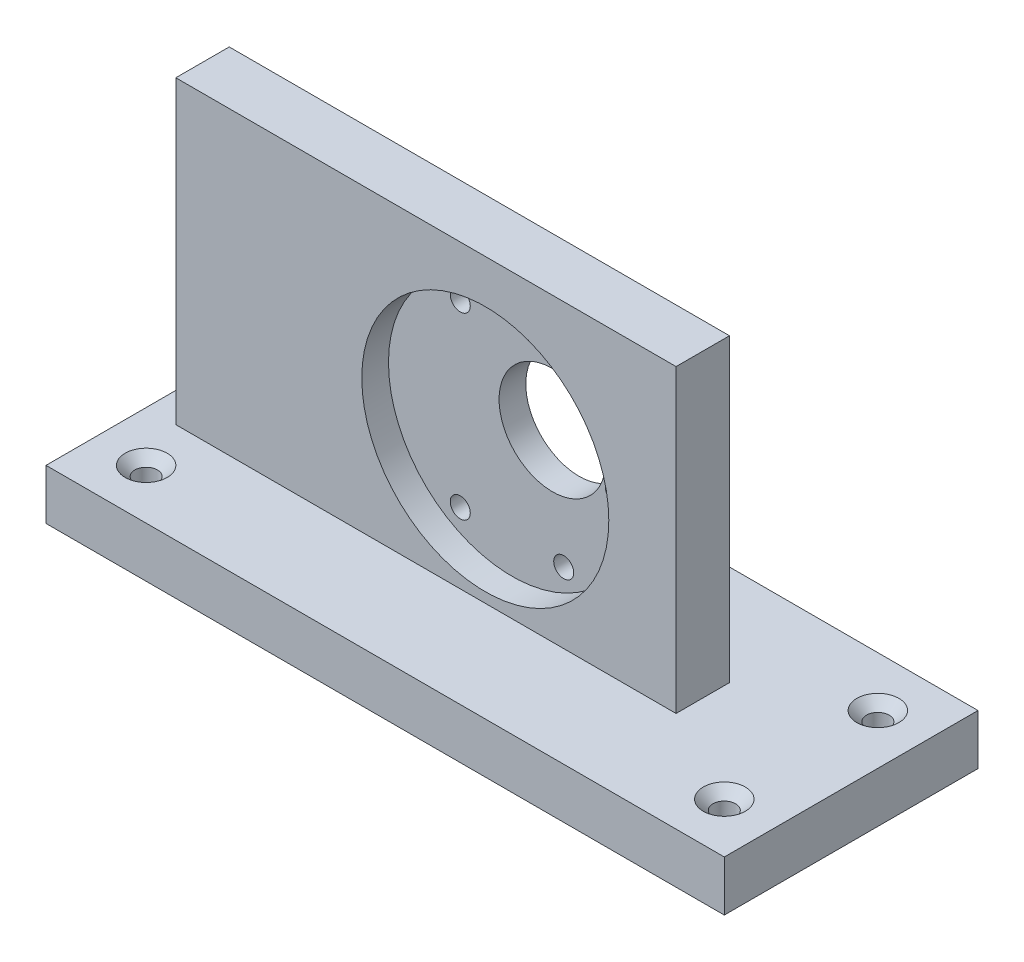
SolidWorks part; units mm, degrees
note: The reader was unsure of these and kept them because the rebuilt part matched: shared geometry of "Sketch3<3>".
other "Markup1"
sketch "Sketch5" plane through (25, 50, 8) normal (0.9645, 0.1424, 0.2224) x (0.1697, 0.3107, -0.9352)
ref_plane "Front Plane" through (0, 0, 0) normal (0, 0, 1) x (1, 0, 0)
ref_plane "Top Plane" through (0, 0, 0) normal (0, 1, 0) x (1, 0, 0)
ref_plane "Right Plane" through (0, 0, 0) normal (1, 0, 0) x (0, 0, -1)
sketch "Sketch3" plane through (0, 0, 0) normal (0, 0, 1) x (1, 0, 0)
  line L1 (-28.575, 50) -> (28.575, 50)
  line L2 (-28.575, 50) -> (-28.575, 0)
  line L3 (-28.575, 0) -> (28.575, 0)
  line L4 (28.575, 50) -> (28.575, 0)
  line L5 (-7.75, 38.4234) -> (7.75, 38.4234) construction
  line L6 (7.75, 38.4234) -> (15.5, 25) construction
  line L7 (15.5, 25) -> (7.75, 11.5766) construction
  line L8 (7.75, 11.5766) -> (-7.75, 11.5766) construction
  line L9 (-7.75, 11.5766) -> (-15.5, 25) construction
  line L10 (-15.5, 25) -> (-7.75, 38.4234) construction
  line L12 (-20.1843, 13.3466) -> (22.8058, 38.167) construction
  circle A5 centre (-7.75, 38.4234) radius 1.5
  circle A6 centre (7.75, 38.4234) radius 1.5
  circle A8 centre (-7.75, 11.5766) radius 1.5
  circle A9 centre (7.75, 11.5766) radius 1.5
  circle A10 centre (15.5, 25) radius 1.5
  circle A11 centre (6.0622, 28.5) radius 8
  point P4 (0, 0)
  point P27 (-11.625, 18.2883)
  point P28 (11.625, 31.7117)
  dimension "D4" = 25
  dimension "D9" = 16
  dimension "D3" = 3
  dimension "D1" = 50
  dimension "D2" = 57.15
  dimension "D6" = 120
  dimension "D7" = 120
  dimension "D8" = 15.5
  dimension "D10" = 6.4234
extrude "Boss-Extrude1" add sketch "Sketch3" along normal blind 8 contours L2 L3 L4 L1
extrude "Cut-Extrude2" cut sketch "Sketch3<3>" along normal blind 10
sketch "Sketch3<3>" plane through (0, 0, 0) normal (0, 0, 1) x (1, 0, 0) same geometry as "Sketch3"
sketch "Sketch4" plane through (0, 0, 8) normal (0, 0, 1) x (1, 0, 0)
  line L0 (-15.5, 25) -> (15.5, 25) construction
  circle A0 centre (0, 25) radius 18.5
  dimension "D1" = 37
extrude "Cut-Extrude3" cut sketch "Sketch4" against normal blind 4 contours A0
sketch "Sketch6" plane through (0, 0, 8) normal (0, 0, 1) x (1, 0, 0)
  line L1 (-50.8, 5) -> (50.8, 5)
  line L2 (-50.8, 5) -> (-50.8, 0)
  line L3 (-50.8, 0) -> (50.8, 0)
  line L4 (50.8, 5) -> (50.8, 0)
  point P4 (0, 0)
  dimension "D1" = 101.6
  dimension "D2" = 5
extrude "Boss-Extrude2" add sketch "Sketch6" against normal blind 23 and the other way blind 15
sketch "Sketch7" plane through (0, 5, 0) normal (0, 1, 0) x (1, 0, 0)
  line L0 (-50.8, -23) -> (-50.8, 15) construction
  line L1 (-50.8, -23) -> (-43.3, -23)
  line L2 (-50.8, -23) -> (-50.8, -15.5)
  line L3 (-50.8, -15.5) -> (-43.3, -15.5)
  line L4 (-43.3, -23) -> (-43.3, -15.5)
  line L5 (-50.8, -4) -> (50.8, -4) construction
  line L6 (50.8, -23) -> (50.8, 15) construction
  line L7 (0, 15) -> (0, -23) construction
  line L8 (50.8, 15) -> (-50.8, 15) construction
  line L9 (50.8, -23) -> (-50.8, -23) construction
  point P18 (-43.3, 7.5)
  point P20 (43.3, -15.5)
  point P21 (43.3, 7.5)
  dimension "D1" = 7.5
hole_wizard "CSK for M3 Flat Head Machine Screw1" positions "Sketch8" profile "Sketch9" countersink size "M3" standard "ANSI Metric" end condition through all
sketch "Sketch8" plane through (0, 5, 0) normal (0, 1, 0) x (1, 0, 0)
  point P0 (-43.3, 7.5)
  point P3 (-43.3, -15.5)
  point P6 (43.3, -15.5)
  point P9 (43.3, 7.5)
sketch "Sketch9" plane through (-43.3, 5, -7.5) normal (1, 0, 0) x (0, 0, 1)
  line L0 (0, 0) -> (0, 5)
  line L1 (0, 5) -> (1.7, 5)
  line L2 (1.7, 5) -> (1.7, 1.45)
  line L3 (1.7, 1.45) -> (3.15, 0)
  line L5 (3.15, 0) -> (0, 0)
  line L6 (-1.7, 1.45) -> (-3.15, 0) construction
  line L11 (0, -6.35) -> (0, 107.95) construction
  dimension "Thru Hole Dia." = 3.4
  dimension "Thru Hole Depth" = 5
  dimension "Near C'Sink Dia." = 6.3
  dimension "Near C'Sink Angle" = 90
extrude "Cut-Extrude6" cut sketch "Sketch16" against normal up to surface (4.826 mm away)
sketch "Sketch16" plane through (-499.2489, 16.8212, -28.3089) normal (0.0361, 0.9993, -0.0009) x (0.0508, -0.0009, 0.9987)
  circle A0 centre (67.5, 464.5) radius 1.7
  circle A2 centre (92.5, 462.5) radius 1.8
  circle A3 centre (113.4, 462.5) radius 1.8
  circle A4 centre (92.5, 401.5) radius 1.8
  circle A5 centre (113.4, 401.5) radius 1.8
  circle A7 centre (67.5, 399.5) radius 1.7
  circle A8 centre (44.5, 399.5) radius 1.7
  circle A9 centre (33.5, 468.8378) radius 1.7
  circle A10 centre (33.5, 435.8378) radius 1.7
  circle A11 centre (44.5, 464.5) radius 1.7
sketch "Sketch17" plane through (0, 5, 0) normal (0, 1, 0) x (1, 0, 0)
  line L1 (-50.8, 15) -> (-25.7177, 15)
  line L2 (-50.8, 15) -> (-50.8, 3.0192)
  line L3 (-50.8, 3.0192) -> (-25.7177, 3.0192)
  line L4 (-25.7177, 15) -> (-25.7177, 3.0192)
extrude "Cut-Extrude7" cut sketch "Sketch17" against normal up to next
sketch "Sketch18" plane through (0, 5, 0) normal (0, 1, 0) x (1, 0, 0)
  line L1 (-28.575, -8) -> (-46.355, -8)
  line L2 (-28.575, -8) -> (-28.575, 0)
  line L3 (-28.575, 0) -> (-46.355, 0)
  line L4 (-46.355, -8) -> (-46.355, 0)
  dimension "D1" = 17.78
  dimension "D2" = 8
extrude "Boss-Extrude3" add sketch "Sketch18" along normal up to vertex (45 mm away)
sketch "Sketch13" plane through (0, 0, 0) normal (0, 0, -1) x (-1, 0, 0)
  line L0 (38.1178, 28.5) -> (-6.0622, 28.5) construction
  circle A5 centre (38.1178, 28.5) radius 4.8006
  circle A7 centre (38.1178, 28.5) radius 6.7056
  dimension "D1" = 9.6012
  dimension "D2" = 1.905
  dimension "D3" = 44.18
extrude "Boss-Extrude4" add sketch "Sketch13" along normal blind 5.08
sketch "Sketch19" plane through (0, 0, 0) normal (0, 0, -1) x (-1, 0, 0)
  circle A0 centre (38.1178, 28.5) radius 4.8006
  dimension "D1" = 9.6012
extrude "Cut-Extrude8" cut sketch "Sketch19" against normal blind 5.08
sketch "Sketch20" plane through (0, 0, 0) normal (0, -1, 0) x (1, 0, 0)
  line L0 (-50.8, -3.0192) -> (-50.8, 23)
  line L1 (-50.8, 23) -> (50.8, 23)
  line L2 (50.8, 23) -> (50.8, -15)
  line L3 (50.8, -15) -> (-25.7177, -15)
  line L4 (-25.7177, -15) -> (-25.7177, -3.0192)
  line L5 (-25.7177, -3.0192) -> (-50.8, -3.0192)
extrude "Boss-Extrude5" add sketch "Sketch20" along normal blind 2.54
